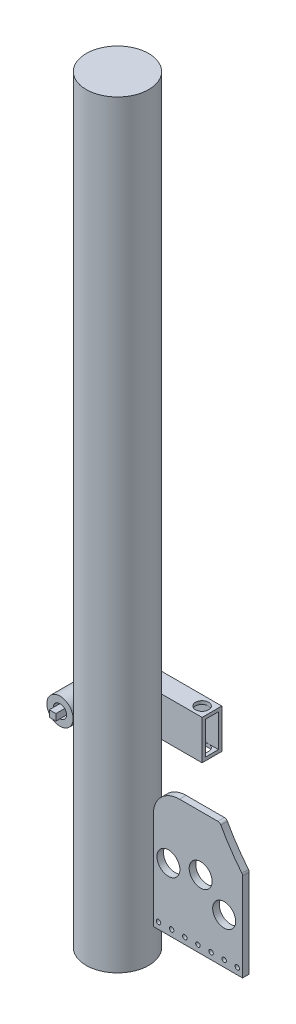
SolidWorks part; units mm, degrees
ref_plane "Front Plane" through (0, 0, 0) normal (0, 0, 1) x (1, 0, 0)
ref_plane "Top Plane" through (0, 0, 0) normal (0, 1, 0) x (1, 0, 0)
ref_plane "Right Plane" through (0, 0, 0) normal (1, 0, 0) x (0, 0, -1)
sketch "Elevation Bar" plane through (0, 0, 0) normal (0, 1, 0) x (1, 0, 0)
  circle A0 centre (0, 0) radius 30.226
  dimension "D1" = 60.452
extrude "Elevation Bar Part" add sketch "Elevation Bar" along normal blind 734.06
sketch "Pole and Drivetrain Pos" plane through (0, 0, 0) normal (0, 0, 1) x (1, 0, 0)
  line L0 (0, 0) -> (172.1794, 0) construction
  line L1 (-30.226, 0) -> (-30.226, 734.06) construction
  line L2 (-30.226, 734.06) -> (30.226, 734.06) construction
  line L3 (30.226, 734.06) -> (30.226, 0) construction
  line L4 (30.226, 0) -> (30.226, 734.06) construction
  line L5 (636.651, 41.275) -> (27.051, 41.275) construction
  line L6 (636.651, 53.975) -> (27.051, 53.975)
  line L7 (636.651, 53.975) -> (636.651, 28.575)
  line L8 (636.651, 28.575) -> (27.051, 28.575)
  line L9 (27.051, 53.975) -> (27.051, 28.575)
  line L10 (-30.226, 93.98) -> (30.226, 93.98) construction
  line L11 (33.2486, 0) -> (-33.2486, 0) construction
  line L12 (30.226, 185.42) -> (-30.226, 185.42) construction
  line L13 (30.226, 276.86) -> (-30.226, 276.86) construction
  line L14 (30.226, 368.3) -> (-30.226, 368.3) construction
  line L15 (30.226, 459.74) -> (-30.226, 459.74) construction
  line L16 (30.226, 551.18) -> (-30.226, 551.18) construction
  line L17 (30.226, 642.62) -> (-30.226, 642.62) construction
  line L18 (30.226, 73.152) -> (750.8896, 73.152) construction
  circle A0 centre (579.501, 41.275) radius 41.275 construction
  circle A1 centre (84.201, 41.275) radius 41.275 construction
  circle A2 centre (331.851, 41.275) radius 41.275 construction
  circle A3 centre (84.201, 41.275) radius 25.4
  point P24 (331.851, 41.275)
  dimension "D2" = 82.55
  dimension "D5" = 50.8
  dimension "D1" = 609.6
  dimension "D3" = 25.4
  dimension "D6" = 93.98
  dimension "D7" = 185.42
  dimension "D8" = 276.86
  dimension "D9" = 368.3
  dimension "D10" = 459.74
  dimension "D11" = 551.18
  dimension "D12" = 642.62
  dimension "D13" = 73.152
  dimension "D14" = 57.15
  dimension "D4" = 57.15
  dimension "D15" = 6.35
sketch "Driving Wheels Geo" plane through (0, 0, 0) normal (0, 0, 1) x (1, 0, 0)
  line L0 (-30.226, 182.88) -> (-30.226, 101.727) construction
  line L1 (55.626, 101.727) -> (30.226, 101.727) construction
  line L2 (-30.226, 0) -> (-30.226, 734.06) construction
  line L3 (30.226, 734.06) -> (30.226, 0) construction
  line L5 (30.226, 101.727) -> (-30.226, 101.727) construction
  line L6 (-30.226, 182.88) -> (30.226, 101.727) construction
  line L7 (31.8135, 101.727) -> (-30.226, 182.88) construction
  line L8 (30.226, 227.417) -> (203.668, 53.975) construction
  line L9 (-42.926, 195.58) -> (44.8729, 195.58) construction
  line L10 (30.226, 73.152) -> (750.8896, 73.152) construction
  line L11 (636.651, 53.975) -> (27.051, 53.975) construction
  line L14 (-42.926, 170.18) -> (44.8729, 170.18) construction
  line L15 (44.8729, 170.18) -> (44.8729, 195.58) construction
  line L16 (81.026, 28.575) -> (81.026, 257.175) construction
  line L17 (32.1729, 195.58) -> (57.5729, 195.58) construction
  line L18 (32.1729, 195.58) -> (32.1729, 170.18) construction
  line L19 (32.1729, 170.18) -> (57.5729, 170.18) construction
  line L20 (57.5729, 195.58) -> (57.5729, 170.18) construction
  line L21 (32.1729, 195.58) -> (57.5729, 170.18) construction
  line L22 (32.1729, 170.18) -> (57.5729, 195.58) construction
  line L23 (636.651, 28.575) -> (27.051, 28.575) construction
  line L24 (284.226, 257.175) -> (81.026, 257.175) construction
  line L25 (284.226, 257.175) -> (284.226, 53.975) construction
  line L26 (81.026, 257.175) -> (30.226, 257.175) construction
  circle A1 centre (55.626, 101.727) radius 25.4
  circle A3 centre (-42.926, 182.88) radius 12.7
  circle A4 centre (81.026, 104.775) radius 50.8 construction
  circle A5 centre (55.626, 101.727) radius 23.8125 construction
  circle A7 centre (284.226, 257.175) radius 203.2 construction
  point P28 (44.8729, 182.88)
  dimension "D1" = 50.8
  dimension "D2" = 1.5875
  dimension "D3" = 52.603
  dimension "D4" = 3.175
  dimension "D5" = 182.88
  dimension "D8" = 101.6
  dimension "D6" = 25.4
  dimension "D13" = 3.175
  dimension "D14" = 50.8
  dimension "D16" = 406.4
  dimension "D7" = 81.153
  dimension "D9" = 45
  dimension "D10" = 53.317
  dimension "D11" = 25.4
  dimension "D12" = 47.752
ref_plane "Plane1" through (0, 182.88, 0) normal (0, 1, 0) x (1, 0, 0)
sketch "Clamp Geo" plane through (0, 182.88, 0) normal (0, 1, 0) x (1, 0, 0)
  line L0 (-42.926, -19.8438) -> (-42.926, 50.8635) construction
  line L3 (27.051, 228.6) -> (27.051, -228.6) construction
  line L4 (50.0464, 31.8135) -> (-49.276, 31.8135)
  line L5 (50.0464, 31.8135) -> (50.0464, 50.8635)
  line L6 (50.0464, 50.8635) -> (-49.276, 50.8635)
  line L7 (-49.276, 31.8135) -> (-49.276, 50.8635)
  line L10 (-46.101, 50.8635) -> (-39.751, 50.8635)
  line L11 (-46.101, 50.8635) -> (-46.101, -19.8438)
  line L12 (-46.101, -19.8438) -> (-39.751, -19.8438)
  line L13 (-39.751, 50.8635) -> (-39.751, -19.8438)
  line L14 (-55.626, 12.7) -> (-30.226, 12.7) construction
  line L15 (-55.626, 12.7) -> (-55.626, -12.7) construction
  line L16 (-55.626, -12.7) -> (-30.226, -12.7) construction
  line L17 (-30.226, 12.7) -> (-30.226, -12.7) construction
  line L18 (-55.626, 12.7) -> (-30.226, -12.7) construction
  line L19 (-55.626, -12.7) -> (-30.226, 12.7) construction
  line L20 (0, -30.226) -> (0, 30.226) construction
  line L21 (-30.226, 0) -> (30.226, 0) construction
  line L22 (-46.101, 46.101) -> (-42.926, 46.101) construction
  line L23 (-39.751, 41.3385) -> (-46.101, 41.3385)
  line L24 (-46.101, 41.3385) -> (-46.101, 50.8635) construction
  line L25 (-39.751, 31.8135) -> (-39.751, 50.8635) construction
  line L26 (50.0464, 41.3385) -> (40.5214, 41.3385) construction
  circle A0 centre (0, 0) radius 30.226 construction
  circle A3 centre (-42.926, 46.101) radius 1.8288
  circle A5 centre (-42.926, 36.576) radius 1.8288
  circle A6 centre (40.5214, 41.3385) radius 6.35
  circle A7 centre (40.5214, 41.3385) radius 13.4704 construction
  point P14 (-42.926, 0)
  point P32 (-39.751, 41.3385)
  point P34 (-46.101, 41.3385)
  point P36 (-42.926, 41.3385)
  point P42 (50.0464, 41.3385)
  dimension "D1" = 60.452
  dimension "D4" = 1.5875
  dimension "D7" = 3.6576
  dimension "D8" = 3.175
  dimension "D10" = 12.7
  dimension "D11" = 3.175
  dimension "D2" = 457.2
  dimension "D3" = 19.05
  dimension "D5" = 6.35
  dimension "D6" = 25.4
  dimension "D9" = 99.3224
  dimension "D13" = 7.1437
extrude "Boss-Extrude1" add sketch "Clamp Geo" along normal blind 19.05 and the other way blind 19.05 separate body contours L6 L13 L4 L5 A6 | L11 L6 L7 L4 | L13 L23 L11 L4 A5 | L23 L13 L6 L11 A3 region at (2.3187, 182.88, -41.3385) region at (-42.926, 182.88, -31.928) region at (-47.6885, 182.88, -41.3385) region at (-42.926, 182.88, -41.453)
sketch "Locked Setting Geo" plane through (0, 182.88, 0) normal (0, 1, 0) x (1, 0, 0)
  line L0 (30.2525, 144.301) -> (91.1428, 108.3583) construction
  line L1 (27.477, 37.9778) -> (77.9656, 123.5104)
  line L2 (27.477, 37.9778) -> (43.8821, 28.2941)
  line L3 (43.8821, 28.2941) -> (94.3707, 113.8267)
  line L4 (77.9656, 123.5104) -> (94.3707, 113.8267)
  line L5 (92.7568, 111.0925) -> (89.5289, 105.6242)
  line L6 (92.7568, 111.0925) -> (31.8664, 147.0352)
  line L7 (31.8664, 147.0352) -> (28.6385, 141.5668)
  line L8 (89.5289, 105.6242) -> (28.6385, 141.5668)
  line L9 (64.7337, 138.6948) -> (51.8221, 116.8213) construction
  line L10 (64.7337, 138.6948) -> (42.8602, 151.6064) construction
  line L11 (42.8602, 151.6064) -> (29.9486, 129.7329) construction
  line L12 (51.8221, 116.8213) -> (29.9486, 129.7329) construction
  line L13 (64.7337, 138.6948) -> (29.9486, 129.7329) construction
  line L14 (42.8602, 151.6064) -> (51.8221, 116.8213) construction
  line L17 (88.6555, 113.5135) -> (87.0416, 110.7793) construction
  line L18 (81.3263, 110.466) -> (84.5542, 115.9344)
  line L19 (84.5542, 115.9344) -> (92.7568, 111.0925) construction
  line L20 (73.1238, 115.3079) -> (89.5289, 105.6242) construction
  line L21 (35.6795, 33.1359) -> (40.5214, 41.3385) construction
  line L22 (50.0464, 50.8635) -> (-49.276, 50.8635) construction
  line L23 (-46.101, 50.8635) -> (-46.101, -19.8438) construction
  line L24 (27.051, 228.6) -> (27.051, -228.6) construction
  circle A1 centre (87.0416, 110.7793) radius 1.8288
  circle A2 centre (78.839, 115.6211) radius 1.8288
  circle A3 centre (40.5214, 41.3385) radius 6.35
  point P10 (47.3411, 134.2138)
  point P28 (81.3263, 110.466)
  point P30 (84.5542, 115.9344)
  point P32 (82.9403, 113.2002)
  point P36 (35.6795, 33.1359)
  point P40 (40.5214, 41.3385)
  point P44 (-17.1792, 28.8062)
  dimension "D6" = 3.6576
  dimension "D9" = 12.7
  dimension "D2" = 19.05
  dimension "D3" = 1.5875
  dimension "D4" = 6.35
  dimension "D5" = 25.4
  dimension "D7" = 3.175
  dimension "D8" = 99.3224
  dimension "D10" = 3.175
  dimension "D11" = 50.8635
  dimension "D12" = 67.3197
sketch "Sketch2" plane through (-49.276, 0, 0) normal (-1, 0, 0) x (0, 0, 1)
  line L0 (-41.3385, 201.93) -> (-41.3385, 163.83) construction
  line L1 (-31.8135, 201.93) -> (-50.8635, 201.93) construction
  line L2 (-31.8135, 163.83) -> (-50.8635, 163.83) construction
  line L3 (-31.8135, 163.83) -> (-31.8135, 201.93) construction
  line L4 (-47.6885, 167.005) -> (-34.9885, 167.005)
  line L5 (-47.6885, 167.005) -> (-47.6885, 198.755)
  line L6 (-47.6885, 198.755) -> (-34.9885, 198.755)
  line L7 (-34.9885, 167.005) -> (-34.9885, 198.755)
  line L8 (-47.6885, 167.005) -> (-34.9885, 198.755) construction
  line L9 (-47.6885, 198.755) -> (-34.9885, 167.005) construction
  point P6 (-41.3385, 182.88)
  dimension "D1" = 3.175
  dimension "D2" = 3.175
extrude "Cut-Extrude2" cut sketch "Sketch2" against normal up to surface (99.3224 mm away) up to face at (50.0464, 182.88, -41.3385)
sketch "Sketch3" plane through (0, 0, -50.8635) normal (0, 0, -1) x (-1, 0, 0)
  line L2 (39.7129, 179.6669) -> (46.1391, 179.6669)
  line L3 (39.7129, 179.6669) -> (39.7129, 186.0931)
  line L4 (39.7129, 186.0931) -> (46.1391, 186.0931)
  line L5 (46.1391, 179.6669) -> (46.1391, 186.0931)
  line L6 (39.7129, 179.6669) -> (46.1391, 186.0931) construction
  line L7 (39.7129, 186.0931) -> (46.1391, 179.6669) construction
  point P0 (42.926, 182.88)
  point P1 (42.926, 182.88)
  dimension "D1" = 6.4262
extrude "Cut-Extrude3" cut sketch "Sketch3" against normal up to surface (19.05 mm away) up to face at (0.3852, 182.88, -31.8135)
extrude "Boss-Extrude2" add sketch "Clamp Geo<3>" along normal blind 3.175 and the other way blind 3.175 separate body contours L13 L4 L11 L12 | L13 L23 L11 L4 A5 | L23 L13 L6 L11 A3 region at (-42.926, 182.88, -5.9849) region at (-42.926, 182.88, -31.928) region at (-42.926, 182.88, -41.453)
sketch "Clamp Geo<3>" plane through (0, 182.88, 0) normal (0, 1, 0) x (1, 0, 0) same geometry as "Clamp Geo"
sketch "Custom Driven Flywheel" plane through (0, 0, 0) normal (0, 0, 1) x (1, 0, 0)
  circle A0 centre (-42.926, 182.88) radius 12.7 construction
  circle A1 centre (-42.926, 182.88) radius 12.7
  circle A2 centre (-42.926, 182.88) radius 6.35
  dimension "D1" = 12.7
extrude "Boss-Extrude3" add sketch "Custom Driven Flywheel" along normal mid plane 25.4 separate body
sketch "Sketch8" plane through (0, 167.005, 0) normal (0, 1, 0) x (1, 0, 0)
  line L0 (-42.926, 47.6885) -> (-42.926, 34.9885) construction
  line L1 (-49.276, 34.9885) -> (-36.576, 34.9885) construction
  line L2 (-49.276, 34.9885) -> (-49.276, 47.6885)
  line L3 (-49.276, 47.6885) -> (-36.576, 47.6885) construction
  line L4 (-36.576, 34.9885) -> (-36.576, 47.6885)
  line L5 (-36.576, 41.3385) -> (-42.926, 41.3385) construction
  line L6 (-42.926, 41.3385) -> (-49.276, 41.3385) construction
  line L7 (-43.8339, 34.9885) -> (-49.276, 34.9885)
  line L8 (-43.8339, 47.6885) -> (-49.276, 47.6885)
  line L9 (-42.0181, 34.9885) -> (-36.576, 34.9885)
  line L10 (-42.0181, 47.6885) -> (-36.576, 47.6885)
  arc A0 (-43.8339, 47.6885) -> (-42.0181, 47.6885) centre (-42.926, 46.101) ccw construction
  arc A2 (-42.0181, 34.9885) -> (-43.8339, 34.9885) centre (-42.926, 36.576) ccw construction
  arc A3 (-43.8339, 47.6885) -> (-42.0181, 47.6885) centre (-42.926, 46.101) ccw
  arc A4 (-42.0181, 34.9885) -> (-43.8339, 34.9885) centre (-42.926, 36.576) ccw
extrude "Boss-Extrude5" add sketch "Sketch8" along normal up to surface (15.875 mm away) separate body up to plane "Plane1"
sketch "Sketch10" plane through (0, 182.88, 0) normal (0, 1, 0) x (1, 0, 0)
  line L0 (-36.576, 41.3385) -> (-49.276, 41.3385) construction
  line L1 (-36.576, 34.9885) -> (-36.576, 47.6885) construction
  line L2 (-49.276, 47.6885) -> (-49.276, 34.9885) construction
  line L3 (-49.276, 34.9885) -> (-43.8339, 34.9885) construction
  line L4 (-46.1391, 34.9885) -> (-39.7129, 34.9885)
  line L5 (-46.1391, 34.9885) -> (-46.1391, 47.6885)
  line L6 (-46.1391, 47.6885) -> (-39.7129, 47.6885)
  line L7 (-39.7129, 34.9885) -> (-39.7129, 47.6885)
  line L8 (-46.1391, 34.9885) -> (-39.7129, 47.6885) construction
  line L9 (-46.1391, 47.6885) -> (-39.7129, 34.9885) construction
  point P6 (-42.926, 41.3385)
  dimension "D1" = 6.4262
extrude "Cut-Extrude5" cut sketch "Sketch10" against normal blind 3.175
ref_plane "Plane2" through (0, 0, 210.82) normal (0, 0, 1) x (1, 0, 0)
ref_plane "Plane3" through (0, 0, 166.37) normal (0, 0, 1) x (1, 0, 0)
sketch "Sketch12" plane through (0, 0, 166.37) normal (0, 0, 1) x (1, 0, 0)
  line L0 (636.651, 41.275) -> (27.051, 41.275) construction
  line L1 (636.651, 41.275) -> (27.051, 41.275) construction
  line L2 (84.201, 41.275) -> (96.901, 41.275) construction
  line L3 (109.601, 41.275) -> (109.601, 85.2691) construction
  circle A0 centre (84.201, 41.275) radius 25.4 construction
  circle A1 centre (84.201, 41.275) radius 25.4
  circle A2 centre (55.626, 101.727) radius 21.1667
  circle A4 centre (86.8604, 107.4259) radius 10.5833
  circle A5 centre (128.651, 41.275) radius 19.05
  circle A7 centre (86.8604, 107.4259) radius 21.1667
  circle A8 centre (109.601, 85.2691) radius 10.5833
  circle A9 centre (109.601, 85.2691) radius 25.4
  circle A10 centre (84.201, 41.275) radius 3.175 construction
  circle A11 centre (96.901, 41.275) radius 3.175 construction
  circle A12 centre (109.601, 41.275) radius 3.175 construction
  circle A13 centre (122.301, 41.275) radius 3.175 construction
  circle A14 centre (135.001, 41.275) radius 3.175 construction
  circle A15 centre (147.701, 41.275) radius 3.175 construction
  circle A16 centre (160.401, 41.275) radius 3.175 construction
  circle A17 centre (173.101, 41.275) radius 3.175 construction
  circle A18 centre (185.801, 41.275) radius 3.175 construction
  circle A19 centre (198.501, 41.275) radius 3.175 construction
  point P3 (55.626, 101.727)
  dimension "D1" = 42.3333
  dimension "D2" = 21.1667
  dimension "D3" = 50.8
  dimension "D4" = 38.1
  dimension "D5" = 42.3333
  dimension "D6" = 21.1667
  dimension "D8" = 6.35
  dimension "D10" = 12.7
  dimension "D9" = 10
sketch "Sketch13" plane through (0, 0, 210.82) normal (0, 0, 1) x (1, 0, 0)
  line L0 (109.601, 72.5691) -> (109.601, 97.9691) construction
  line L2 (90.551, 72.5691) -> (90.551, 97.9691)
  line L4 (154.051, 72.5691) -> (154.051, 97.9691)
  line L5 (147.701, 85.2691) -> (147.701, 41.275) construction
  line L6 (109.601, 85.2691) -> (154.051, 85.2691) construction
  line L7 (90.551, 85.2691) -> (109.601, 85.2691) construction
  line L8 (90.551, 97.9691) -> (109.601, 97.9691)
  line L9 (90.551, 72.5691) -> (109.601, 72.5691)
  line L10 (109.601, 97.9691) -> (154.051, 97.9691)
  line L11 (154.051, 72.5691) -> (109.601, 72.5691)
  circle A0 centre (109.601, 85.2691) radius 3.175 construction
  circle A1 centre (96.901, 85.2691) radius 3.175 construction
  circle A2 centre (147.701, 85.2691) radius 3.175 construction
  point P0 (109.601, 85.2691)
  dimension "D2" = 6.35
  dimension "D3" = 6.35
  dimension "D6" = 6.35
  dimension "D1" = 25.4
  dimension "D4" = 12.7
  dimension "D5" = 6.35
ref_plane "Plane5" through (0, 0, 146.177) normal (0, 0, 1) x (1, 0, 0)
sketch "Sketch15" plane through (0, 0, 146.177) normal (0, 0, 1) x (1, 0, 0)
  line L0 (90.551, 72.5691) -> (109.601, 72.5691) construction
  line L1 (154.051, 72.5691) -> (109.601, 72.5691) construction
  line L2 (154.051, 72.5691) -> (154.051, 97.9691) construction
  line L3 (109.601, 97.9691) -> (154.051, 97.9691) construction
  line L4 (90.551, 97.9691) -> (109.601, 97.9691) construction
  line L5 (90.551, 72.5691) -> (90.551, 97.9691) construction
  line L6 (90.551, 72.5691) -> (109.601, 72.5691)
  line L7 (154.051, 72.5691) -> (109.601, 72.5691)
  line L8 (154.051, 72.5691) -> (154.051, 97.9691)
  line L9 (109.601, 97.9691) -> (154.051, 97.9691)
  line L10 (90.551, 97.9691) -> (109.601, 97.9691)
  line L11 (90.551, 72.5691) -> (90.551, 97.9691)
  line L12 (90.551, 28.575) -> (109.601, 28.575)
  line L13 (154.051, 28.575) -> (109.601, 28.575)
  line L14 (154.051, 28.575) -> (154.051, 53.975)
  line L15 (109.601, 53.975) -> (154.051, 53.975)
  line L16 (90.551, 53.975) -> (109.601, 53.975)
  line L17 (90.551, 28.575) -> (90.551, 53.975)
  line L18 (154.051, 28.575) -> (90.551, 53.975) construction
  line L19 (109.601, 53.975) -> (109.601, 28.575) construction
  line L20 (154.051, 41.275) -> (90.551, 41.275) construction
  circle A0 centre (109.601, 85.2691) radius 3.175 construction
  circle A1 centre (109.601, 85.2691) radius 3.175
  circle A2 centre (109.601, 41.275) radius 3.175 construction
  dimension "D5" = 6.35
  dimension "D1" = 68.3916
  dimension "D2" = 68.3916
  dimension "D3" = 19.05
  dimension "D4" = 25.4
ref_plane "Plane6" through (0, 53.975, 0) normal (0, 1, 0) x (1, 0, 0)
sketch "Sketch16" plane through (0, 53.975, 0) normal (0, 1, 0) x (1, 0, 0)
  line L0 (27.051, -127) -> (27.051, 127)
  line L1 (33.401, 120.65) -> (33.401, 107.95) construction
  line L2 (27.051, 127) -> (39.751, 127)
  line L3 (27.051, 127) -> (27.051, -127)
  line L4 (27.051, -127) -> (39.751, -127)
  line L5 (39.751, 127) -> (39.751, -127)
  line L6 (33.401, 120.65) -> (33.401, 127) construction
  line L7 (135.001, -166.37) -> (135.001, -127) construction
  line L8 (636.651, 0) -> (27.051, 0) construction
  line L9 (128.651, 127) -> (141.351, 127)
  line L14 (128.651, 127) -> (128.651, -127)
  line L15 (128.651, -127) -> (141.351, -127)
  line L16 (141.351, 127) -> (141.351, -127)
  line L17 (128.651, 127) -> (141.351, -127) construction
  line L18 (128.651, -127) -> (141.351, 127) construction
  line L19 (135.001, -120.65) -> (135.001, -107.95) construction
  line L20 (135.001, -127) -> (135.001, -120.65) construction
  circle A0 centre (33.401, 120.65) radius 3.175
  circle A1 centre (33.401, 107.95) radius 3.175
  circle A2 centre (33.401, 95.25) radius 3.175
  circle A3 centre (33.401, 82.55) radius 3.175
  circle A4 centre (33.401, 69.85) radius 3.175
  circle A5 centre (33.401, 57.15) radius 3.175
  circle A6 centre (33.401, 44.45) radius 3.175
  circle A7 centre (33.401, 31.75) radius 3.175
  circle A8 centre (33.401, 19.05) radius 3.175
  circle A9 centre (33.401, 6.35) radius 3.175
  circle A10 centre (33.401, -6.35) radius 3.175
  circle A11 centre (33.401, -19.05) radius 3.175
  circle A12 centre (33.401, -31.75) radius 3.175
  circle A13 centre (33.401, -44.45) radius 3.175
  circle A14 centre (33.401, -57.15) radius 3.175
  circle A15 centre (33.401, -69.85) radius 3.175
  circle A16 centre (33.401, -82.55) radius 3.175
  circle A17 centre (33.401, -95.25) radius 3.175
  circle A18 centre (33.401, -107.95) radius 3.175
  circle A19 centre (33.401, -120.65) radius 3.175
  circle A40 centre (135.001, -120.65) radius 3.175
  circle A41 centre (135.001, -107.95) radius 3.175
  circle A42 centre (135.001, -95.25) radius 3.175
  circle A43 centre (135.001, -82.55) radius 3.175
  circle A44 centre (135.001, -69.85) radius 3.175
  circle A45 centre (135.001, -57.15) radius 3.175
  circle A46 centre (135.001, -44.45) radius 3.175
  circle A47 centre (135.001, -31.75) radius 3.175
  circle A48 centre (135.001, -19.05) radius 3.175
  circle A49 centre (135.001, -6.35) radius 3.175
  circle A50 centre (135.001, 6.35) radius 3.175
  circle A51 centre (135.001, 19.05) radius 3.175
  circle A52 centre (135.001, 31.75) radius 3.175
  circle A53 centre (135.001, 44.45) radius 3.175
  circle A54 centre (135.001, 57.15) radius 3.175
  circle A55 centre (135.001, 69.85) radius 3.175
  circle A56 centre (135.001, 82.55) radius 3.175
  circle A57 centre (135.001, 95.25) radius 3.175
  circle A58 centre (135.001, 107.95) radius 3.175
  circle A59 centre (135.001, 120.65) radius 3.175
  point P3 (27.051, 0)
  point P9 (135.001, -166.37)
  point P51 (135.001, 0)
  dimension "D3" = 6.35
  dimension "D1" = 254
  dimension "D2" = 12.7
  dimension "D4" = 6.35
  dimension "D6" = 12.7
  dimension "D10" = 6.35
  dimension "D12" = 12.7
  dimension "D5" = 20
  dimension "D11" = 20
sketch "Sketch18" plane through (0, 53.975, 0) normal (0, 1, 0) x (1, 0, 0)
  line L0 (39.751, -36.5125) -> (128.651, -36.5125)
  line L1 (39.751, 127) -> (39.751, -127) construction
  line L2 (128.651, 127) -> (128.651, -127) construction
  line L3 (636.651, 0) -> (27.051, 0) construction
  line L4 (39.751, -49.2125) -> (128.651, -49.2125)
  line L5 (39.751, -36.5125) -> (39.751, -49.2125)
  line L6 (128.651, -36.5125) -> (128.651, -49.2125)
  line L7 (39.751, -42.8625) -> (128.651, -42.8625) construction
  line L8 (46.101, -42.8625) -> (58.801, -42.8625) construction
  line L9 (-403.733, 0) -> (403.733, 0) construction
  line L10 (46.101, 42.8625) -> (58.801, 42.8625) construction
  line L11 (39.751, 42.8625) -> (128.651, 42.8625) construction
  line L12 (128.651, 36.5125) -> (128.651, 49.2125)
  line L13 (39.751, 36.5125) -> (39.751, 49.2125)
  line L14 (39.751, 49.2125) -> (128.651, 49.2125)
  line L15 (39.751, 36.5125) -> (128.651, 36.5125)
  circle A0 centre (46.101, -42.8625) radius 3.175
  circle A1 centre (58.801, -42.8625) radius 3.175
  circle A2 centre (71.501, -42.8625) radius 3.175
  circle A3 centre (84.201, -42.8625) radius 3.175
  circle A4 centre (96.901, -42.8625) radius 3.175
  circle A5 centre (109.601, -42.8625) radius 3.175
  circle A6 centre (122.301, -42.8625) radius 3.175
  circle A7 centre (122.301, 42.8625) radius 3.175
  circle A8 centre (109.601, 42.8625) radius 3.175
  circle A9 centre (96.901, 42.8625) radius 3.175
  circle A10 centre (84.201, 42.8625) radius 3.175
  circle A11 centre (71.501, 42.8625) radius 3.175
  circle A12 centre (58.801, 42.8625) radius 3.175
  circle A13 centre (46.101, 42.8625) radius 3.175
  dimension "D4" = 6.35
  dimension "D1" = 36.5125
  dimension "D2" = 12.7
  dimension "D3" = 6.35
  dimension "D6" = 12.7
  dimension "D5" = 7
sketch "Sketch17" plane through (0, 0, 0) normal (0, 0, 1) x (1, 0, 0)
  line L0 (41.021, 53.975) -> (41.021, 135.255)
  line L2 (127.381, 126.8514) -> (127.381, 53.975)
  line L6 (128.651, 53.975) -> (141.351, 53.975) construction
  line L9 (636.651, 53.975) -> (27.051, 53.975) construction
  line L10 (41.021, 53.975) -> (41.021, 41.275)
  line L11 (41.021, 41.275) -> (127.381, 41.275)
  line L13 (127.381, 53.975) -> (127.381, 41.275)
  line L14 (55.626, 101.727) -> (55.626, 41.275) construction
  line L16 (66.421, 160.655) -> (103.5286, 160.655)
  line L17 (50.0464, 163.83) -> (-49.276, 163.83) construction
  circle A0 centre (55.626, 101.727) radius 11.1125
  circle A1 centre (86.8604, 107.4259) radius 11.1125
  circle A2 centre (109.601, 85.2691) radius 11.1125
  circle A6 centre (284.226, 257.175) radius 203.2 construction
  arc A7 (106.3086, 159.0138) -> (126.6678, 128.8564) centre (284.226, 257.175) ccw
  arc A8 (41.021, 135.255) -> (66.421, 160.655) centre (66.421, 135.255) cw
  arc A9 (127.381, 126.8514) -> (126.6678, 128.8564) centre (124.206, 126.8514) ccw
  arc A10 (103.5286, 160.655) -> (106.3086, 159.0138) centre (103.5286, 157.48) cw
  point P25 (127.381, 127.9857)
  dimension "D1" = 22.225
  dimension "D6" = 25.4
  dimension "D7" = 3.175
  dimension "D4" = 12.7
  dimension "D5" = 13.97
  dimension "D3" = 13.97
  dimension "D2" = 3.175
sketch "Sketch19" plane through (0, 0, 0) normal (0, 0, 1) x (1, 0, 0)
  line L0 (46.101, 47.625) -> (122.301, 47.625) construction
  line L1 (46.101, 41.275) -> (46.101, 53.975) construction
  line L2 (636.651, 41.275) -> (27.051, 41.275) construction
  line L3 (636.651, 53.975) -> (27.051, 53.975) construction
  line L4 (46.101, 47.625) -> (58.801, 47.625) construction
  circle A0 centre (46.101, 47.625) radius 2.1527
  circle A1 centre (58.801, 47.625) radius 2.1527
  circle A2 centre (71.501, 47.625) radius 2.1527
  circle A3 centre (84.201, 47.625) radius 2.1527
  circle A4 centre (96.901, 47.625) radius 2.1527
  circle A5 centre (109.601, 47.625) radius 2.1527
  circle A6 centre (122.301, 47.625) radius 2.1527
  dimension "D2" = 4.3053
  dimension "D1" = 6.35
  dimension "D4" = 12.7
  dimension "D3" = 7
extrude "Boss-Extrude6" add sketch "Sketch17" along normal blind 6.35 separate body
extrude "Cut-Extrude7" cut sketch "Sketch19" along normal blind 6.35
sketch "Sketch20" [suppressed] plane through (0, 0, 6.35) normal (0, 0, 1) x (1, 0, 0)
  line L0 (41.021, 56.515) -> (127.381, 56.515)
  line L1 (41.021, 135.255) -> (41.021, 41.275) construction
  line L2 (127.381, 41.275) -> (127.381, 126.8514) construction
  line L10 (41.021, 135.255) -> (41.021, 41.275)
  line L11 (41.021, 41.275) -> (127.381, 41.275)
  line L12 (127.381, 41.275) -> (127.381, 126.8514)
  line L13 (103.5286, 160.655) -> (66.421, 160.655)
  line L14 (41.021, 135.255) -> (41.021, 41.275) construction
  line L19 (41.021, 124.8884) -> (127.381, 124.8884)
  line L20 (46.101, 124.8884) -> (54.991, 140.2864)
  line L21 (54.991, 140.2864) -> (63.881, 124.8884)
  line L22 (63.881, 124.8884) -> (72.771, 140.2864)
  line L23 (72.771, 140.2864) -> (81.661, 124.8884)
  line L25 (54.991, 140.2864) -> (72.771, 140.2864)
  line L26 (72.771, 140.2864) -> (108.331, 140.2864)
  line L27 (81.661, 124.8884) -> (90.551, 140.2864)
  line L28 (90.551, 140.2864) -> (99.441, 124.8884)
  line L29 (99.441, 124.8884) -> (108.331, 140.2864)
  line L30 (108.331, 140.2864) -> (117.221, 124.8884)
  line L31 (54.991, 140.2864) -> (63.881, 155.6843)
  line L32 (63.881, 155.6843) -> (72.771, 140.2864)
  line L33 (46.101, 124.8884) -> (46.101, 140.2864)
  line L34 (46.101, 140.2864) -> (54.991, 140.2864)
  line L35 (72.771, 140.2864) -> (81.661, 155.6843)
  line L36 (63.881, 155.6843) -> (61.8536, 155.6843)
  line L37 (81.661, 155.6843) -> (90.551, 140.2864)
  line L38 (90.551, 140.2864) -> (99.441, 155.6843)
  line L39 (99.441, 155.6843) -> (108.331, 140.2864)
  line L40 (63.881, 155.6843) -> (99.441, 155.6843)
  line L41 (117.221, 124.8884) -> (108.331, 109.4905)
  line L42 (108.331, 109.4905) -> (99.441, 124.8884)
  line L43 (117.221, 124.8884) -> (117.221, 109.4905)
  line L44 (117.221, 109.4905) -> (108.331, 109.4905)
  line L45 (117.221, 109.4905) -> (117.221, 100.9813)
  line L46 (117.221, 100.9813) -> (108.331, 109.4905)
  line L47 (46.101, 56.515) -> (54.991, 71.9129)
  line L48 (54.991, 71.9129) -> (63.881, 56.515)
  line L49 (63.881, 56.515) -> (72.771, 71.9129)
  line L50 (72.771, 71.9129) -> (81.661, 56.515)
  line L51 (81.661, 56.515) -> (90.551, 71.9129)
  line L52 (90.551, 71.9129) -> (99.441, 56.515)
  line L53 (54.991, 71.9129) -> (72.771, 71.9129)
  line L54 (90.551, 71.9129) -> (72.771, 71.9129)
  line L55 (46.101, 56.515) -> (46.101, 71.9129)
  line L56 (46.101, 71.9129) -> (54.991, 71.9129)
  line L57 (46.101, 71.9129) -> (46.101, 87.091)
  line L58 (46.3026, 86.9618) -> (54.991, 71.9129)
  line L59 (81.661, 87.3109) -> (65.4806, 87.3109)
  line L60 (81.661, 87.3109) -> (90.551, 71.9129)
  line L61 (72.771, 71.9129) -> (81.661, 87.3109)
  line L62 (64.3061, 86.5746) -> (72.771, 71.9129)
  line L63 (54.991, 71.9129) -> (63.0894, 85.9398)
  line L65 (125.5178, 67.8066) -> (105.9602, 67.8066)
  line L66 (99.441, 56.515) -> (105.9602, 67.8066)
  line L67 (112.4794, 56.515) -> (105.9602, 67.8066)
  line L68 (112.4794, 56.515) -> (118.9986, 67.8066)
  line L69 (118.9986, 67.8066) -> (125.5178, 56.515)
  line L70 (125.5178, 56.515) -> (125.5178, 67.8066)
  line L71 (105.9602, 67.8066) -> (92.9218, 67.8066)
  circle A0 centre (46.101, 47.625) radius 2.1526 construction
  arc A2 (46.101, 140.2864) -> (61.8536, 155.6843) centre (66.421, 135.255) cw
  circle A4 centre (86.8604, 107.4259) radius 17.4625 construction
  arc A5 (127.381, 126.8514) -> (126.6678, 128.8564) centre (124.206, 126.8514) ccw
  arc A6 (106.3086, 159.0138) -> (126.6678, 128.8564) centre (284.226, 257.175) ccw
  arc A7 (106.3086, 159.0138) -> (103.5286, 160.655) centre (103.5286, 157.48) ccw
  arc A8 (66.421, 160.655) -> (41.021, 135.255) centre (66.421, 135.255) ccw
  arc A12 (66.421, 160.655) -> (41.021, 135.255) centre (66.421, 135.255) ccw construction
  circle A13 centre (86.8604, 107.4259) radius 11.1125 construction
  circle A14 centre (109.601, 85.2691) radius 17.4625 construction
  circle A15 centre (109.601, 85.2691) radius 11.1125 construction
  circle A16 centre (55.626, 101.727) radius 17.4625 construction
  circle A17 centre (55.626, 101.727) radius 11.1125 construction
  arc A18 (46.101, 87.091) -> (65.4806, 87.3109) centre (55.626, 101.727) ccw
  dimension "D4" = 5.08
  dimension "D3" = 6.35
  dimension "D7" = 6.35
  dimension "D8" = 6.35
  dimension "D1" = 8.89
  dimension "D5" = 60
  dimension "D6" = 17.78
  dimension "D9" = 60
  dimension "D10" = 5.08
  dimension "D11" = 60
  dimension "D12" = 60
  dimension "D13" = 60
  dimension "D14" = 60
  dimension "D2" = 0
sketch "Sketch21" [suppressed] plane through (0, 0, 6.35) normal (0, 0, 1) x (1, 0, 0)
  line L0 (117.221, 124.8884) -> (117.221, 109.4905) construction
  line L1 (117.221, 109.4905) -> (108.331, 109.4905) construction
  line L2 (117.221, 109.4905) -> (117.221, 100.9813) construction
  line L3 (117.221, 100.9813) -> (108.331, 109.4905) construction
  line L4 (72.771, 140.2864) -> (81.661, 124.8884) construction
  line L5 (81.661, 124.8884) -> (90.551, 140.2864) construction
  line L6 (90.551, 140.2864) -> (99.441, 124.8884) construction
  line L7 (72.771, 140.2864) -> (81.661, 155.6843) construction
  line L8 (81.661, 155.6843) -> (90.551, 140.2864) construction
  line L9 (90.551, 140.2864) -> (99.441, 155.6843) construction
  line L10 (72.771, 140.2864) -> (108.331, 140.2864) construction
  line L11 (99.441, 124.8884) -> (108.331, 140.2864) construction
  line L12 (108.331, 140.2864) -> (117.221, 124.8884) construction
  line L13 (99.441, 155.6843) -> (108.331, 140.2864) construction
  line L14 (41.021, 56.515) -> (127.381, 56.515) construction
  line L15 (108.331, 109.4905) -> (99.441, 124.8884) construction
  line L16 (46.101, 124.8884) -> (54.991, 140.2864) construction
  line L17 (46.101, 124.8884) -> (46.101, 140.2864) construction
  line L18 (54.991, 140.2864) -> (63.881, 124.8884) construction
  line L19 (63.881, 124.8884) -> (72.771, 140.2864) construction
  line L20 (54.991, 140.2864) -> (72.771, 140.2864) construction
  line L21 (54.991, 140.2864) -> (63.881, 155.6843) construction
  line L22 (46.101, 140.2864) -> (54.991, 140.2864) construction
  line L23 (41.021, 124.8884) -> (127.381, 124.8884) construction
  line L24 (117.221, 124.8884) -> (108.331, 109.4905) construction
  line L25 (63.881, 155.6843) -> (99.441, 155.6843) construction
  line L26 (63.881, 155.6843) -> (61.8536, 155.6843) construction
  line L27 (63.881, 155.6843) -> (72.771, 140.2864) construction
  line L28 (54.991, 71.9129) -> (63.0894, 85.9398) construction
  line L29 (46.3026, 86.9618) -> (54.991, 71.9129) construction
  line L30 (72.771, 71.9129) -> (81.661, 56.515) construction
  line L31 (81.661, 56.515) -> (90.551, 71.9129) construction
  line L32 (90.551, 71.9129) -> (99.441, 56.515) construction
  line L33 (99.441, 56.515) -> (105.9602, 67.8066) construction
  line L34 (90.551, 71.9129) -> (72.771, 71.9129) construction
  line L35 (81.661, 87.3109) -> (90.551, 71.9129) construction
  line L36 (54.991, 71.9129) -> (63.881, 56.515) construction
  line L37 (63.881, 56.515) -> (72.771, 71.9129) construction
  line L38 (54.991, 71.9129) -> (72.771, 71.9129) construction
  line L39 (72.771, 71.9129) -> (81.661, 87.3109) construction
  line L40 (64.3061, 86.5746) -> (72.771, 71.9129) construction
  line L41 (46.101, 56.515) -> (54.991, 71.9129) construction
  line L42 (46.101, 56.515) -> (46.101, 71.9129) construction
  line L43 (46.101, 71.9129) -> (54.991, 71.9129) construction
  line L44 (105.9602, 67.8066) -> (92.9218, 67.8066) construction
  line L45 (46.101, 71.9129) -> (46.101, 87.091) construction
  line L46 (81.661, 87.3109) -> (65.4806, 87.3109) construction
  line L47 (125.5178, 67.8066) -> (105.9602, 67.8066) construction
  line L48 (125.5178, 56.515) -> (125.5178, 67.8066) construction
  line L49 (118.9986, 67.8066) -> (125.5178, 56.515) construction
  line L50 (112.4794, 56.515) -> (118.9986, 67.8066) construction
  line L51 (112.4794, 56.515) -> (105.9602, 67.8066) construction
  line L52 (117.221, 124.8884) -> (117.221, 109.4905)
  line L53 (117.221, 109.4905) -> (108.331, 109.4905)
  line L54 (117.221, 109.4905) -> (117.221, 100.9813)
  line L55 (117.221, 100.9813) -> (108.331, 109.4905)
  line L56 (72.771, 140.2864) -> (81.661, 124.8884)
  line L57 (81.661, 124.8884) -> (90.551, 140.2864)
  line L58 (90.551, 140.2864) -> (99.441, 124.8884)
  line L59 (72.771, 140.2864) -> (81.661, 155.6843)
  line L60 (81.661, 155.6843) -> (90.551, 140.2864)
  line L61 (90.551, 140.2864) -> (99.441, 155.6843)
  line L62 (72.771, 140.2864) -> (108.331, 140.2864)
  line L63 (99.441, 124.8884) -> (108.331, 140.2864)
  line L64 (108.331, 140.2864) -> (117.221, 124.8884)
  line L65 (99.441, 155.6843) -> (108.331, 140.2864)
  line L66 (41.021, 56.515) -> (127.381, 56.515)
  line L67 (108.331, 109.4905) -> (99.441, 124.8884)
  line L68 (46.101, 124.8884) -> (54.991, 140.2864)
  line L69 (46.101, 124.8884) -> (46.101, 140.2864)
  line L70 (54.991, 140.2864) -> (63.881, 124.8884)
  line L71 (63.881, 124.8884) -> (72.771, 140.2864)
  line L72 (54.991, 140.2864) -> (72.771, 140.2864)
  line L73 (54.991, 140.2864) -> (63.881, 155.6843)
  line L74 (46.101, 140.2864) -> (54.991, 140.2864)
  line L75 (41.021, 124.8884) -> (127.381, 124.8884)
  line L76 (117.221, 124.8884) -> (108.331, 109.4905)
  line L77 (63.881, 155.6843) -> (99.441, 155.6843)
  line L78 (63.881, 155.6843) -> (61.8536, 155.6843)
  line L79 (63.881, 155.6843) -> (72.771, 140.2864)
  line L80 (54.991, 71.9129) -> (63.0894, 85.9398)
  line L81 (46.3026, 86.9618) -> (54.991, 71.9129)
  line L82 (72.771, 71.9129) -> (81.661, 56.515)
  line L83 (81.661, 56.515) -> (90.551, 71.9129)
  line L84 (90.551, 71.9129) -> (99.441, 56.515)
  line L85 (99.441, 56.515) -> (105.9602, 67.8066)
  line L86 (90.551, 71.9129) -> (72.771, 71.9129)
  line L87 (81.661, 87.3109) -> (90.551, 71.9129)
  line L88 (54.991, 71.9129) -> (63.881, 56.515)
  line L89 (63.881, 56.515) -> (72.771, 71.9129)
  line L90 (54.991, 71.9129) -> (72.771, 71.9129)
  line L91 (72.771, 71.9129) -> (81.661, 87.3109)
  line L92 (64.3061, 86.5746) -> (72.771, 71.9129)
  line L93 (46.101, 56.515) -> (54.991, 71.9129)
  line L94 (46.101, 56.515) -> (46.101, 71.9129)
  line L95 (46.101, 71.9129) -> (54.991, 71.9129)
  line L96 (105.9602, 67.8066) -> (92.9218, 67.8066)
  line L97 (46.101, 71.9129) -> (46.101, 87.091)
  line L98 (81.661, 87.3109) -> (65.4806, 87.3109)
  line L99 (125.5178, 67.8066) -> (105.9602, 67.8066)
  line L100 (125.5178, 56.515) -> (125.5178, 67.8066)
  line L101 (118.9986, 67.8066) -> (125.5178, 56.515)
  line L102 (112.4794, 56.515) -> (118.9986, 67.8066)
  line L103 (112.4794, 56.515) -> (105.9602, 67.8066)
  arc A0 (61.8536, 155.6843) -> (46.101, 140.2864) centre (66.421, 135.255) ccw construction
  arc A1 (46.101, 87.091) -> (65.4806, 87.3109) centre (55.626, 101.727) ccw construction
  arc A2 (61.8536, 155.6843) -> (46.101, 140.2864) centre (66.421, 135.255) ccw
  arc A3 (46.101, 87.091) -> (65.4806, 87.3109) centre (55.626, 101.727) ccw
equation "\"D4@Pole and Drivetrain Pos\"=\"D14@Pole and Drivetrain Pos\""
equation "\"D5@Sketch17\"=\"D3@Sketch17\""
